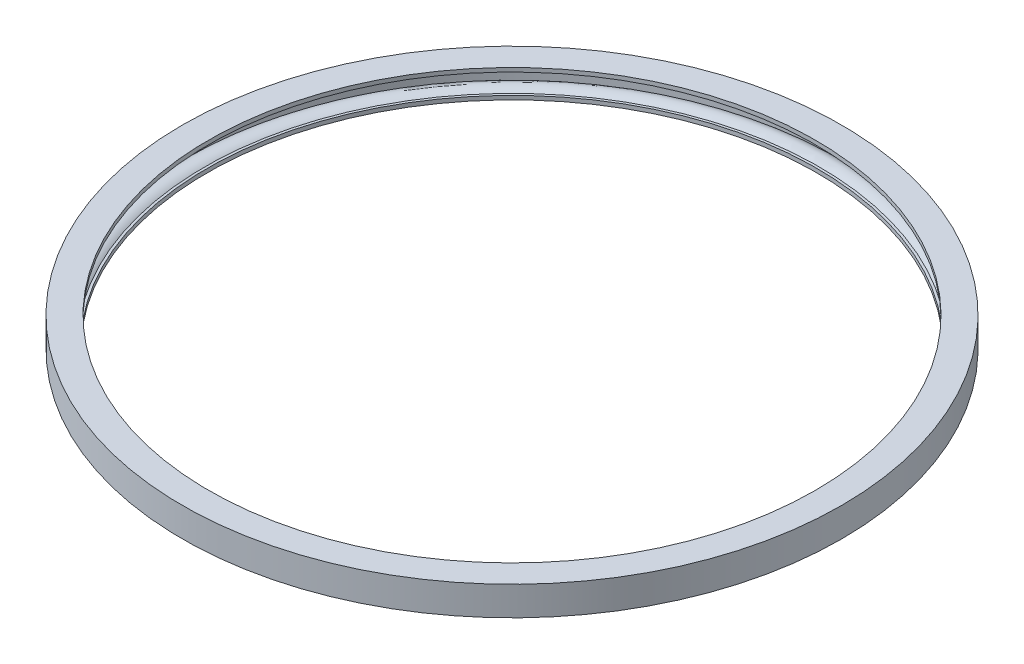
SolidWorks part; units mm, degrees
ref_plane "Front" through (0, 0, 0) normal (0, 0, 1) x (1, 0, 0)
ref_plane "Top" through (0, 0, 0) normal (0, 1, 0) x (1, 0, 0)
ref_plane "Right" through (0, 0, 0) normal (1, 0, 0) x (0, 0, -1)
sketch "Sketch2" plane through (19.1209, -95.8671, 65.5706) normal (0.1986, 0, -0.9801) x (-0.9801, 0, -0.1986)
  line L0 (-263.3326, 5.2216) -> (390.7174, 5.2216) construction
  line L1 (-263.3326, 5.2216) -> (63.6924, 5.2216) construction
  line L2 (-253.8076, 8.9005) -> (-253.8076, -16.4995)
  line L3 (-272.8576, 8.9005) -> (-272.8576, -16.4995)
  line L4 (-249.8076, 7.1619) -> (-249.8076, 11.2216)
  line L5 (-249.8076, 11.2216) -> (-219.5385, 11.2216)
  line L6 (-219.5385, 11.2216) -> (-276.8576, 11.2216)
  line L7 (-276.8576, 11.2216) -> (-276.8576, -18.8205)
  line L8 (-276.8576, -18.8205) -> (-251.2782, -18.8205)
  line L9 (-251.2782, -18.8205) -> (-251.2782, -14.7608)
  line L10 (-272.8576, -3.7995) -> (-253.8076, -3.7995) construction
  line L11 (-263.3326, -3.7995) -> (-263.3326, -18.8205) construction
  line L12 (-263.3326, -3.7995) -> (-263.3326, 11.2216) construction
  line L13 (-251.2782, -14.7608) -> (-253.8076, -14.7608)
  line L14 (-249.8076, 7.1619) -> (-253.8076, 7.1619)
  line L15 (63.6924, 5.2216) -> (63.6924, 39.475) construction
  line L16 (63.6924, -18.7995) -> (63.6924, 49.1889) construction
  arc A0 (-263.3326, -12.8205) -> (-272.8576, -16.4995) centre (-263.3326, -26.9903) ccw construction
  arc A1 (-253.8076, -16.4995) -> (-263.3326, -12.8205) centre (-263.3326, -26.9903) ccw construction
  arc A2 (-263.3326, 5.2216) -> (-253.8076, 8.9005) centre (-263.3326, 19.3914) ccw construction
  arc A3 (-272.8576, 8.9005) -> (-263.3326, 5.2216) centre (-263.3326, 19.3914) ccw construction
  arc A4 (-263.3326, -12.8205) -> (-272.8576, -16.4995) centre (-263.3326, -26.9903) ccw
  arc A5 (-253.8076, -16.4995) -> (-263.3326, -12.8205) centre (-263.3326, -26.9903) ccw
  arc A6 (-263.3326, 5.2216) -> (-253.8076, 8.9005) centre (-263.3326, 19.3914) ccw
  arc A7 (-272.8576, 8.9005) -> (-263.3326, 5.2216) centre (-263.3326, 19.3914) ccw
  dimension "D1" = 4
  dimension "D2" = 6
  dimension "D3" = 4
revolve "Revolve1" add sketch "Sketch2" angle 360 about L15 region at (272.3478, -89.3168, 116.8797)
